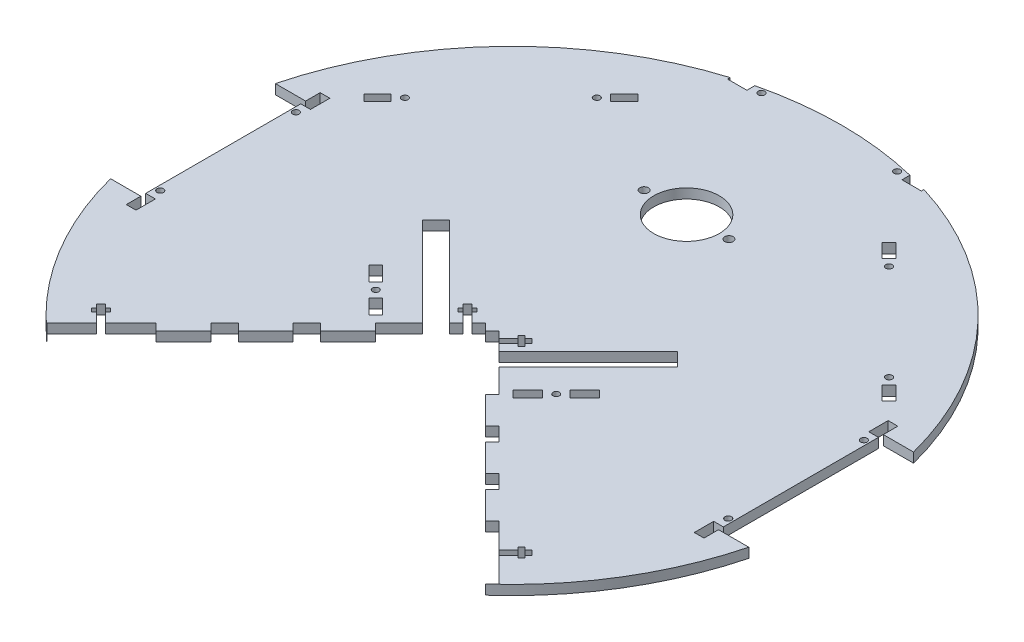
SolidWorks part; units mm, degrees
ref_plane "Front Plane" through (0, 0, 0) normal (0, 0, 1) x (1, 0, 0)
ref_plane "Top Plane" through (0, 0, 0) normal (0, 1, 0) x (1, 0, 0)
ref_plane "Right Plane" through (0, 0, 0) normal (1, 0, 0) x (0, 0, -1)
sketch "Sketch1" plane through (0, 0, 0) normal (0, 1, 0) x (1, 0, 0)
  circle A0 centre (0, 0) radius 215.9
  dimension "D1" = 431.8
extrude "Base Plate" add sketch "Sketch1" along normal blind 6.35
sketch "Sketch2" plane through (0, 6.35, 0) normal (0, 1, 0) x (1, 0, 0)
  line L0 (0, -17.4608) -> (-143.6841, -161.1449)
  line L1 (0, -36.2008) -> (0, -54.9716) construction
  line L2 (0, -17.4608) -> (143.6841, -161.1449)
  circle A0 centre (0, 0) radius 215.9 construction
  arc A1 (-143.6841, -161.1449) -> (143.6841, -161.1449) centre (0, 0) ccw
  dimension "D1" = 203.2
  dimension "D2" = 45
extrude "V Funnel Cut" cut sketch "Sketch2" against normal through all
sketch "Sketch4" plane through (0, 6.35, 0) normal (0, 1, 0) x (1, 0, 0)
  line L0 (0, 54.2551) -> (0, 121.7464) construction
  line L1 (-213.36, 53.975) -> (-191.77, 53.975)
  line L2 (-215.9, 51.435) -> (-215.9, -51.435)
  line L3 (-213.36, -53.975) -> (-191.77, -53.975)
  line L4 (-189.23, 51.435) -> (-189.23, -51.435)
  line L5 (-17.8666, 0) -> (24.1783, 0) construction
  line L6 (-215.9, -69.5481) -> (-215.9, -224.3367) construction
  line L8 (-215.9, 53.975) -> (-189.23, 53.975)
  line L9 (-215.9, 53.975) -> (-215.9, -53.975)
  line L10 (-215.9, -53.975) -> (-189.23, -53.975)
  line L11 (-189.23, 53.975) -> (-189.23, -53.975)
  arc A0 (-213.36, -53.975) -> (-215.9, -51.435) centre (-213.36, -51.435) cw
  arc A1 (-191.77, -53.975) -> (-189.23, -51.435) centre (-191.77, -51.435) ccw
  arc A2 (-189.23, 51.435) -> (-191.77, 53.975) centre (-191.77, 51.435) ccw
  arc A3 (-213.36, 53.975) -> (-215.9, 51.435) centre (-213.36, 51.435) ccw
  arc A4 (143.6841, -161.1449) -> (-143.6841, -161.1449) centre (0, 0) ccw construction
  arc M13 (143.6841, -161.1449) -> (-143.6841, -161.1449) centre (0, 0) ccw
  dimension "D5" = 2.54
  dimension "D4" = 2.54
  dimension "D1" = 26.67
  dimension "D3" = 107.95
extrude "Wheel Hole Slot" cut sketch "Sketch4" against normal through all contours A3 L8 L9 | L1 A3 L2 M13 | L4 A2 L1 L3 A1 M13 | A2 L11 L8 | A0 L3 L2 M13 | L10 A0 L9 | A1 L10 L11 region at (-215.3326, 6.35, -53.4076) region at (-213.8321, 6.35, -40.3773) region at (-201.5273, 6.35, 0) region at (-189.7974, 6.35, -53.4076) region at (-213.8321, 6.35, 40.3773) region at (-215.3326, 6.35, 53.4076) region at (-189.7974, 6.35, 53.4076)
mirror "Wheel Slot Mirror" about plane through (0, 0, 0) normal (1, 0, 0) of "Wheel Hole Slot"
sketch "Sketch6" plane through (0, 6.35, 0) normal (0, 1, 0) x (1, 0, 0)
  line L0 (-35.921, -53.3819) -> (-29.5658, -59.7371) construction
  line L1 (0, -17.4608) -> (-143.6841, -161.1449) construction
  line L2 (143.6841, -161.1449) -> (0, -17.4608) construction
  line B0 (-61.3685, -23.4443) -> (-71.1005, -13.7123)
  line B1 (-61.3685, -23.4443) -> (-65.8586, -27.9344)
  line B2 (-71.1005, -13.7123) -> (-75.5906, -18.2024)
  line B3 (-65.8586, -27.9344) -> (-75.5906, -18.2024)
  line B4 (-52.3882, -32.4245) -> (-42.6562, -42.1565)
  line B5 (-56.8783, -36.9147) -> (-47.1463, -46.6467)
  line B6 (-42.6562, -42.1565) -> (-47.1463, -46.6467)
  line B7 (-52.3882, -32.4245) -> (-56.8783, -36.9147)
  circle B8 centre (-59.1234, -30.1795) radius 2.0955
  dimension "D1" = 50.8
  dimension "D2" = 12.7
sketch_block_instance "BoltTab-1"
sketch_block "BoltTab" parameters "D1"=4.191, "D2"=6.35, "D3"=6.35
extrude "Arm Post Connector" cut sketch "Sketch6" against normal through all
mirror "Arm Post Connector Mirror" about plane through (0, 0, 0) normal (1, 0, 0) of "Arm Post Connector"
sketch "Sketch8" plane through (0, 0, 0) normal (0, -1, 0) x (1, 0, 0)
  line L0 (-189.23, -63.5) -> (-189.23, -50.8) construction
  line L1 (-189.23, -63.5) -> (-182.88, -63.5) construction
  line L2 (-182.88, -63.5) -> (-182.88, -50.8) construction
  line L3 (-189.23, -50.8) -> (-182.88, -50.8) construction
  line L4 (-189.23, -63.5) -> (-189.23, -50.8)
  line L5 (-189.23, -63.5) -> (-182.88, -63.5)
  line L6 (-182.88, -63.5) -> (-182.88, -50.8)
  line L7 (-189.23, -50.8) -> (-182.88, -50.8)
  line L8 (-189.23, 50.8) -> (-182.88, 50.8) construction
  line L9 (-189.23, 63.5) -> (-189.23, 50.8) construction
  line L10 (-182.88, 63.5) -> (-182.88, 50.8) construction
  line L11 (-189.23, 63.5) -> (-182.88, 63.5) construction
  line L12 (-189.23, 50.8) -> (-182.88, 50.8)
  line L13 (-189.23, 63.5) -> (-189.23, 50.8)
  line L14 (-182.88, 63.5) -> (-182.88, 50.8)
  line L15 (-189.23, 63.5) -> (-182.88, 63.5)
  line L16 (-189.23, -46.5836) -> (-182.88, -46.5836) construction
  line L17 (-189.23, -42.3164) -> (-182.88, -42.3164) construction
  line L18 (-189.23, -46.5836) -> (-182.88, -46.5836) construction
  line L19 (-189.23, -42.3164) -> (-182.88, -42.3164) construction
  line L20 (-186.055, -42.3164) -> (-186.055, -46.5836) construction
  line L21 (-189.23, 42.3164) -> (-182.88, 42.3164) construction
  line L22 (-189.23, 46.5836) -> (-182.88, 46.5836) construction
  line L23 (-189.23, 42.3164) -> (-182.88, 42.3164) construction
  line L24 (-189.23, 46.5836) -> (-182.88, 46.5836) construction
  line L25 (-186.055, 42.3164) -> (-186.055, 46.5836) construction
  circle A0 centre (-186.055, -44.45) radius 2.1336
  circle A1 centre (-186.055, 44.45) radius 2.1336
extrude "Motor Mount Connector" cut sketch "Sketch8" against normal through all
mirror "Motor Mount Connector Mirror" about plane through (0, 0, 0) normal (1, 0, 0) of "Motor Mount Connector"
sketch "Sketch9" plane through (0, 0, 0) normal (0, -1, 0) x (1, 0, 0)
  line L0 (-63.5, -204.6423) -> (-63.5, -210.9923) construction
  line L1 (-63.5, -204.6423) -> (-50.8, -204.6423) construction
  line L2 (-50.8, -204.6423) -> (-50.8, -210.9923) construction
  line L3 (-63.5, -210.9923) -> (-50.8, -210.9923) construction
  line L4 (-63.5, -204.6423) -> (-63.5, -210.9923)
  line L5 (-63.5, -204.6423) -> (-50.8, -204.6423)
  line L6 (-50.8, -204.6423) -> (-50.8, -210.9923)
  line L7 (-63.5, -210.9923) -> (-50.8, -210.9923)
  line L8 (-46.5836, -204.6423) -> (-46.5836, -210.9923) construction
  line L9 (-42.3164, -204.6423) -> (-42.3164, -210.9923) construction
  line L10 (-46.5836, -204.6423) -> (-46.5836, -210.9923) construction
  line L11 (-42.3164, -204.6423) -> (-42.3164, -210.9923) construction
  line L12 (-46.5836, -207.8173) -> (-42.3164, -207.8173) construction
  line L13 (42.3164, -204.6423) -> (42.3164, -210.9923) construction
  line L14 (46.5836, -204.6423) -> (46.5836, -210.9923) construction
  line L15 (42.3164, -204.6423) -> (42.3164, -210.9923) construction
  line L16 (46.5836, -204.6423) -> (46.5836, -210.9923) construction
  line L17 (50.8, -210.9923) -> (63.5, -210.9923)
  line L18 (63.5, -210.9923) -> (63.5, -204.6423)
  line L19 (63.5, -204.6423) -> (50.8, -204.6423)
  line L20 (50.8, -204.6423) -> (50.8, -210.9923)
  line L21 (50.8, -210.9923) -> (63.5, -210.9923)
  line L22 (63.5, -210.9923) -> (63.5, -204.6423)
  line L23 (63.5, -204.6423) -> (50.8, -204.6423)
  line L24 (50.8, -204.6423) -> (50.8, -210.9923)
  line L25 (42.3164, -207.8173) -> (46.5836, -207.8173) construction
  circle A0 centre (-44.45, -207.8173) radius 2.1336
  circle A1 centre (44.45, -207.8173) radius 2.1336
  dimension "D1" = 0
extrude "Back Mount Connector" cut sketch "Sketch9" against normal through all
sketch "Sketch10" plane through (0, 0, 0) normal (0, -1, 0) x (1, 0, 0)
  line L0 (-174.2858, -77.1614) -> (-165.3055, -86.1417) construction
  line L1 (-165.3055, -86.1417) -> (-160.8154, -81.6515) construction
  line L2 (-160.8154, -81.6515) -> (-169.7956, -72.6713) construction
  line L3 (-169.7956, -72.6713) -> (-174.2858, -77.1614) construction
  line L4 (-93.4635, -157.9837) -> (-84.4832, -166.964) construction
  line L5 (-84.4832, -166.964) -> (-79.9931, -162.4738) construction
  line L6 (-79.9931, -162.4738) -> (-88.9733, -153.4936) construction
  line L7 (-88.9733, -153.4936) -> (-93.4635, -157.9837) construction
  line L8 (-174.2858, -77.1614) -> (-165.3055, -86.1417)
  line L9 (-165.3055, -86.1417) -> (-160.8154, -81.6515)
  line L10 (-160.8154, -81.6515) -> (-169.7956, -72.6713)
  line L11 (-169.7956, -72.6713) -> (-174.2858, -77.1614)
  line L12 (-93.4635, -157.9837) -> (-84.4832, -166.964)
  line L13 (-84.4832, -166.964) -> (-79.9931, -162.4738)
  line L14 (-79.9931, -162.4738) -> (-88.9733, -153.4936)
  line L15 (-88.9733, -153.4936) -> (-93.4635, -157.9837)
  line L16 (-157.8339, -84.633) -> (-162.3241, -89.1231) construction
  line L17 (-154.8166, -87.6504) -> (-159.3067, -92.1405) construction
  line L18 (-94.9721, -147.4948) -> (-99.4623, -151.9849) construction
  line L19 (-91.9548, -150.5121) -> (-96.4449, -155.0023) construction
  line L20 (-157.8339, -84.633) -> (-162.3241, -89.1231) construction
  line L21 (-154.8166, -87.6504) -> (-159.3067, -92.1405) construction
  line L22 (-94.9721, -147.4948) -> (-99.4623, -151.9849) construction
  line L23 (-91.9548, -150.5121) -> (-96.4449, -155.0023) construction
  line L25 (-157.0616, -89.8954) -> (-160.079, -86.8781) construction
  line L26 (-97.2172, -149.7398) -> (-94.1998, -152.7572) construction
  circle A0 centre (-158.5703, -88.3867) radius 2.1336
  circle A1 centre (-95.7085, -151.2485) radius 2.1336
extrude "Side Ass Connector" cut sketch "Sketch10" against normal through all
mirror "Side Ass Connector Mirror" about plane through (0, 0, 0) normal (1, 0, 0) of "Side Ass Connector"
sketch "Sketch11" plane through (0, 6.35, 0) normal (0, 1, 0) x (1, 0, 0)
  line L0 (0, 61.4305) -> (0, 100.7164) construction
  line L1 (-82.8279, 215.9) -> (68.7629, 215.9) construction
  circle A0 centre (0, 114.3) radius 21.463
  circle A2 centre (27.7813, 114.3) radius 2.7781 construction
  circle A3 centre (-27.7813, 114.3) radius 2.7781 construction
  circle A4 centre (27.7813, 114.3) radius 2.7781
  circle A5 centre (-27.7813, 114.3) radius 2.7781
  arc A6 (209.0443, 53.975) -> (63.5, 206.3506) centre (0, 0) ccw construction
  dimension "D1" = 42.926
  dimension "D2" = 101.6
extrude "Caster Wheel Hole" cut sketch "Sketch11" against normal through all
sketch "Sketch12" plane through (8.7304, 0, 8.7304) normal (0.7071, 0, 0.7071) x (0.7071, 0, -0.7071)
  line L0 (-164.9233, 6.35) -> (-164.9233, 0) construction
  line L1 (-215.5467, 6.35) -> (-164.9233, 6.35)
  line L2 (-215.5467, 6.35) -> (-215.5467, 0)
  line L3 (-215.5467, 0) -> (-164.9233, 0)
  line L4 (-164.9233, 6.35) -> (-164.9233, 0)
  line L5 (-12.3467, 0) -> (-215.5467, 0) construction
  line L6 (-12.3467, 6.35) -> (-215.5467, 6.35) construction
  line L7 (-139.5233, 6.35) -> (-126.8233, 6.35)
  line L8 (-139.5233, 6.35) -> (-139.5233, 0)
  line L9 (-139.5233, 0) -> (-126.8233, 0)
  line L10 (-126.8233, 6.35) -> (-126.8233, 0)
  line L11 (-139.5233, 0) -> (-139.5233, 6.35) construction
  line L12 (-126.8233, 6.35) -> (-126.8233, 0) construction
  line L13 (-101.4233, 0) -> (-101.4233, 6.35) construction
  line L14 (-101.4233, 6.35) -> (-88.7233, 6.35)
  line L15 (-101.4233, 6.35) -> (-101.4233, 0)
  line L16 (-101.4233, 0) -> (-88.7233, 0)
  line L17 (-88.7233, 6.35) -> (-88.7233, 0)
  line L18 (-88.7233, 6.35) -> (-88.7233, 0) construction
  line L19 (-63.3233, 0) -> (-63.3233, 6.35) construction
  line L20 (-63.3233, 6.35) -> (-12.3467, 6.35)
  line L21 (-63.3233, 6.35) -> (-63.3233, 0)
  line L22 (-63.3233, 0) -> (-12.3467, 0)
  line L23 (-12.3467, 6.35) -> (-12.3467, 0)
extrude "V Funnel Tabs" cut sketch "Sketch12" against normal blind 6.35
mirror "V Funnel Tab Mirror" about plane through (0, 0, 0) normal (1, 0, 0) of "V Funnel Tabs"
sketch "Sketch13" plane through (0, 6.35, 0) normal (0, 1, 0) x (1, 0, 0)
  line L0 (-11.6893, -29.1502) -> (-20.6696, -38.1304)
  line L1 (-11.6893, -29.1502) -> (-74.5511, 33.7116)
  line L2 (-20.6696, -38.1304) -> (-83.5314, 24.7314)
  line L3 (-74.5511, 33.7116) -> (-83.5314, 24.7314)
  line L4 (-40.5361, -49.0167) -> (-36.0459, -53.5068) construction
  line L8 (-36.0459, -53.5068) -> (-54.0065, -71.4673) construction
  line L10 (46.9371, -96.7568) -> (41.6854, -91.5051) construction
  line L11 (-137795.0233, 137745.2035) -> (172087.8094, -172137.6291) construction
  dimension "D1" = 88.9
  dimension "D2" = 12.7
extrude "Peg Clearance" cut sketch "Sketch13" against normal through all
mirror "Peg Clearance Mirror" about plane through (0, 0, 0) normal (1, 0, 0) of "Peg Clearance"
sketch "Sketch14" plane through (0, 6.35, 0) normal (0, 1, 0) x (1, 0, 0)
  line L0 (-39.3557, 10.2056) -> (-2.7686, -26.3816) construction
  line L1 (-16.1795, -24.66) -> (-4.4901, -12.9707) construction
  line L3 (0, -17.4608) -> (-4.4901, -12.9707) construction
  line L4 (-16.1795, -24.66) -> (-74.5511, 33.7116) construction
  line B0 (-11.8435, -20.3241) -> (-8.8261, -17.3067)
  line B1 (-17.2675, -8.8652) -> (-15.6331, -7.2308)
  line B2 (-15.6331, -7.2308) -> (-13.3881, -9.4759)
  line B3 (-13.3881, -9.4759) -> (-15.0225, -11.1103)
  line B4 (-15.0225, -11.1103) -> (-8.8261, -17.3067)
  line B5 (-17.2675, -8.8652) -> (-19.6024, -6.5304)
  line B6 (-19.6024, -6.5304) -> (-22.6198, -9.5477)
  line B7 (-20.2849, -11.8826) -> (-22.6198, -9.5477)
  line B8 (-18.0398, -14.1277) -> (-11.8435, -20.3241)
  line B9 (-19.6743, -15.7621) -> (-18.0398, -14.1277)
  line B10 (-21.9193, -13.517) -> (-19.6743, -15.7621)
  line B11 (-20.2849, -11.8826) -> (-21.9193, -13.517)
sketch_block_instance "TSlot-1"
sketch_block "TSlot" parameters "D1"=3.302, "D2"=3.175
extrude "V Funnel T Slot 1" cut sketch "Sketch14" against normal through all
sketch "Sketch15" plane through (0, 6.35, 0) normal (0, 1, 0) x (1, 0, 0)
  line L0 (-105.2777, -164.0051) -> (-173.117, -96.1657) construction
  line L1 (-112.3781, -120.8587) -> (-107.888, -125.3488) construction
  line L2 (-143.9339, -161.3948) -> (-148.4241, -156.9046) construction
  line L3 (-148.4241, -156.9046) -> (-143.1663, -151.6469) construction
  line B0 (-131.9098, -140.3904) -> (-128.8924, -137.373)
  line B1 (-137.3338, -128.9315) -> (-135.6994, -127.2971)
  line B2 (-135.6994, -127.2971) -> (-133.4544, -129.5422)
  line B3 (-133.4544, -129.5422) -> (-135.0888, -131.1766)
  line B4 (-135.0888, -131.1766) -> (-128.8924, -137.373)
  line B5 (-137.3338, -128.9315) -> (-139.6687, -126.5967)
  line B6 (-139.6687, -126.5967) -> (-142.6861, -129.614)
  line B7 (-140.3512, -131.9489) -> (-142.6861, -129.614)
  line B8 (-138.1062, -134.194) -> (-131.9098, -140.3904)
  line B9 (-139.7406, -135.8284) -> (-138.1062, -134.194)
  line B10 (-141.9856, -133.5833) -> (-139.7406, -135.8284)
  line B11 (-140.3512, -131.9489) -> (-141.9856, -133.5833)
sketch_block_instance "TSlot-3"
extrude "V Funnel T Slot 2" cut sketch "Sketch15" against normal through all
mirror "Mirror1" about plane through (0, 0, 0) normal (1, 0, 0) of "V Funnel T Slot 2", "V Funnel T Slot 1"
